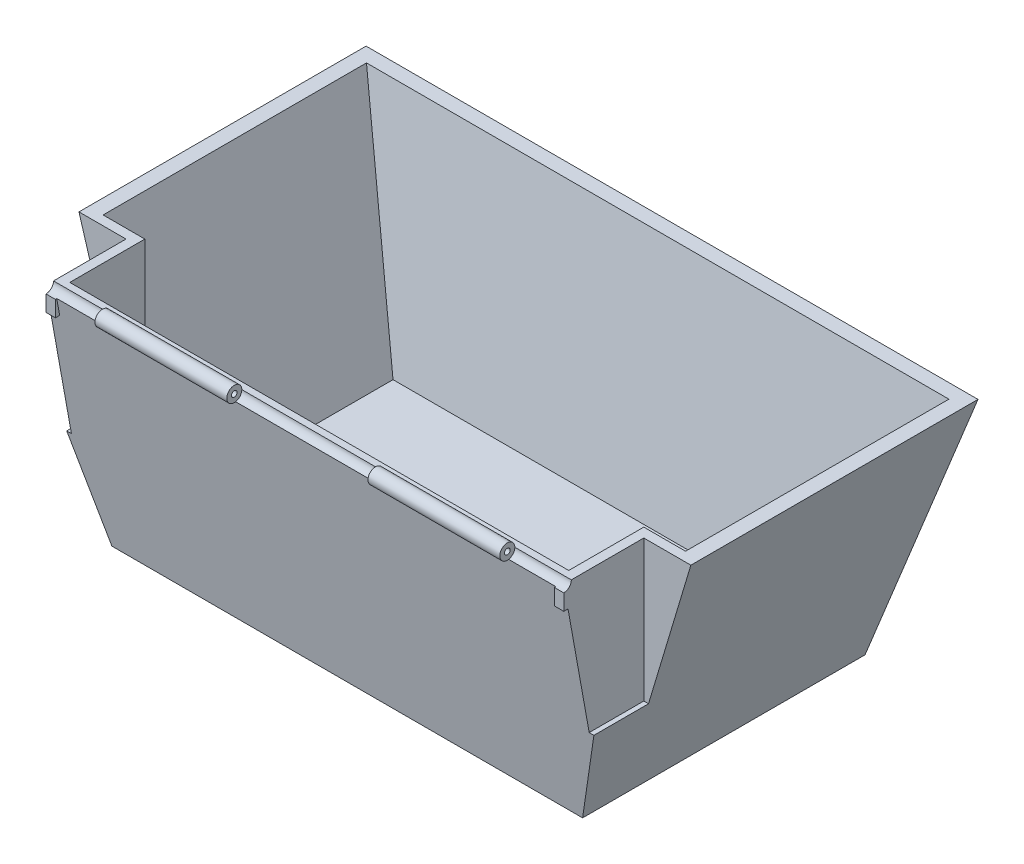
SolidWorks part; units mm, degrees
ref_plane "前视基准面" through (0, 0, 0) normal (0, 0, 1) x (1, 0, 0)
ref_plane "上视基准面" through (0, 0, 0) normal (0, 1, 0) x (1, 0, 0)
ref_plane "右视基准面" through (0, 0, 0) normal (1, 0, 0) x (0, 0, -1)
other "Configuration Table"
sketch "草图1" plane through (0, 0, 0) normal (0, 1, 0) x (1, 0, 0)
  line L1 (-50, -30) -> (50, -30)
  line L2 (-50, -30) -> (-50, 30)
  line L3 (-50, 30) -> (50, 30)
  line L4 (50, -30) -> (50, 30)
  line L5 (-50, -30) -> (50, 30) construction
  line L6 (-50, 30) -> (50, -30) construction
  point P0 (0, 0)
  dimension "D2" = 60
  dimension "D1" = 100
ref_plane "基准面1" through (0, 50, 0) normal (0, 1, 0) x (1, 0, 0)
sketch "草图2" plane through (0, 50, 0) normal (0, 1, 0) x (1, 0, 0)
  line L1 (-65, -39) -> (65, -39)
  line L2 (-65, -39) -> (-65, 39)
  line L3 (-65, 39) -> (65, 39)
  line L4 (65, -39) -> (65, 39)
  line L5 (-65, -39) -> (65, 39) construction
  line L6 (-65, 39) -> (65, -39) construction
  point P0 (0, 0)
  dimension "D1" = 130
  dimension "D2" = 78
loft "放样1" add profiles "草图1", "草图2" connector at (-50, 0, -30) connector at (-65, 50, -39)
shell "抽壳1" thickness 3 removed face at (0, 50, 0)
sketch "草图4" plane through (0, 0, 0) normal (1, 0, 0) x (0, 0, -1)
  line L0 (-39, 50) -> (39, 50) construction
  line L1 (-39, 50) -> (-22, 50)
  line L2 (-39, 50) -> (-39, 20)
  line L3 (-39, 20) -> (-22, 20)
  line L4 (-22, 50) -> (-22, 20)
  dimension "D1" = 17
  dimension "D2" = 30
extrude "切除-拉伸1" cut sketch "草图4" along normal through all from offset 55
extrude "切除-拉伸2" cut sketch "草图4<2>" against normal through all from offset 55 offset against normal yes
sketch "草图4<2>" plane through (0, 0, 0) normal (1, 0, 0) x (0, 0, -1) same geometry as "草图4"
extrude "凸台-拉伸1" add sketch "草图4<3>" against normal blind 2 from offset 55
sketch "草图4<3>" plane through (0, 0, 0) normal (1, 0, 0) x (0, 0, -1) same geometry as "草图4"
extrude "凸台-拉伸2" add sketch "草图4<4>" along normal blind 2 from offset 55 offset against normal yes
sketch "草图4<4>" plane through (0, 0, 0) normal (1, 0, 0) x (0, 0, -1) same geometry as "草图4"
sketch "草图5" plane through (0, 0, 0) normal (1, 0, 0) x (0, 0, -1)
  circle A0 centre (-39, 50) radius 1.6
  circle A1 centre (-39, 50) radius 0.6
  dimension "D1" = 1
  dimension "D2" = 1.2
extrude "凸台-拉伸3" add sketch "草图5" against normal up to surface (55 mm away) from surface contours A0 up to face at (-55, 33.6845, 28.1833) starting at face at (55, 33.6845, 28.1833)
extrude "切除-拉伸3" cut sketch "草图5<3>" against normal through all both and the other way through all contours A1
sketch "草图5<3>" plane through (0, 0, 0) normal (1, 0, 0) x (0, 0, -1) same geometry as "草图5"
extrude "切除-拉伸4" cut sketch "草图5<4>" against normal blind 15 and the other way blind 15
sketch "草图5<4>" plane through (0, 0, 0) normal (1, 0, 0) x (0, 0, -1) same geometry as "草图5"
extrude "切除-拉伸5" cut sketch "草图5<5>" against normal through all from offset 43 offset against normal yes
sketch "草图5<5>" plane through (0, 0, 0) normal (1, 0, 0) x (0, 0, -1) same geometry as "草图5"
extrude "切除-拉伸6" cut sketch "草图5<6>" along normal through all from offset 43
sketch "草图5<6>" plane through (0, 0, 0) normal (1, 0, 0) x (0, 0, -1) same geometry as "草图5"
sketch "草图6" plane through (55, 0, 0) normal (1, 0, 0) x (0, 0, -1)
  line L0 (-33.6, 20) -> (-39, 50)
  line L1 (-30, 0) -> (-33.6, 20) construction
  line L2 (-22, 50) -> (39, 50) construction
  line L3 (-39, 50) -> (-39, 20)
  line L4 (-39, 20) -> (-33.6, 20)
  line L9 (-39, 45) -> (-38.1, 45)
  line M7 (-39, 20) -> (-33.6, 20)
  dimension "D1" = 5
extrude "切除-拉伸8" cut sketch "草图6" against normal through all contours L9 L3 L0 M7 region at (55, 29.5238, 37.1571)
sketch "草图7" plane through (0, 0, 22) normal (0, 0, -1) x (-1, 0, 0)
  line L0 (-65, 50) -> (-56, 20)
  line L1 (-50, 0) -> (-65, 50) construction
  line L2 (-65, 50) -> (-53, 50)
  line L3 (-53, 50) -> (-53, 20)
  line L4 (-53, 20) -> (-56, 20)
  line L5 (65, 50) -> (56, 20)
  line L6 (50, 0) -> (65, 50) construction
  line L7 (65, 50) -> (53, 50)
  line L8 (53, 50) -> (53, 20)
  line L9 (53, 20) -> (56, 20)
extrude "凸台-拉伸4" add sketch "草图7" along normal blind 2
equation "\"rwh\"= ( 60 / 100 )'长宽比"
equation "\"r\"= 1.00'比例"
equation "\"D1@草图1\"=\"r\" * 100"
equation "\"D2@草图1\"=\"r\"*60"
equation "\"D1@草图2\"=\"r\"*130"
equation "\"D2@草图2\"=\"r\"*78"
